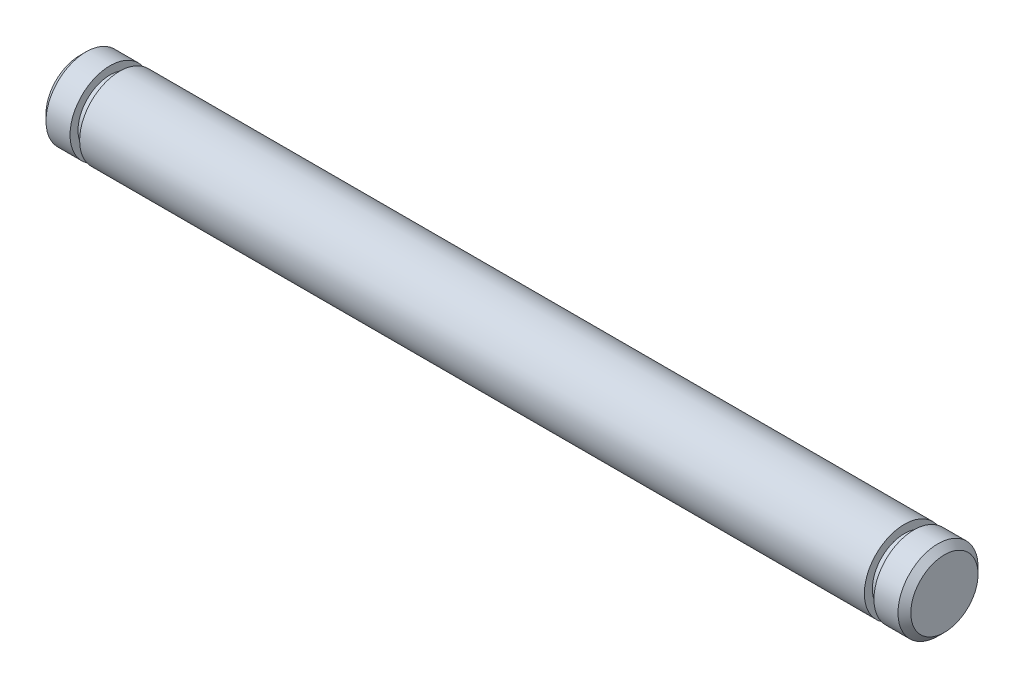
SolidWorks part; units mm, degrees
ref_plane "Front Plane" through (0, 0, 0) normal (0, 0, 1) x (1, 0, 0)
ref_plane "Top Plane" through (0, 0, 0) normal (0, 1, 0) x (1, 0, 0)
ref_plane "Right Plane" through (0, 0, 0) normal (1, 0, 0) x (0, 0, -1)
ref_axis "Axis_X" through (-4.6, 0, 0) along (1, 0, 0)
ref_axis "Axis_Y" through (0, 2.75, 0) along (0, -1, 0)
ref_axis "Axis_Z" through (0, 0, -2.75) along (0, 0, 1)
sketch "Sketch1" plane through (0, 0, 0) normal (0, 0, 1) x (1, 0, 0)
  line L0 (0.6, 2.5) -> (49.6, 2.5)
  line L1 (-1.9, 0) -> (52.1, 0) construction
  line L2 (-1.9, 0) -> (-1.9, 2.1)
  line L3 (-1.5, 2.5) -> (0, 2.5)
  line L4 (52.1, 0) -> (52.1, 2.1)
  line L5 (50.2, 2.5) -> (51.7, 2.5)
  line L6 (0, 2.5) -> (0, 2)
  line L7 (0, 2) -> (0.6, 2)
  line L8 (0.6, 2.5) -> (0.6, 2)
  line L9 (-1.9, 2.1) -> (-1.5, 2.5)
  line L10 (49.6, 2.5) -> (49.6, 2)
  line L11 (49.6, 2) -> (50.2, 2)
  line L12 (50.2, 2.5) -> (50.2, 2)
  line L13 (51.7, 2.5) -> (52.1, 2.1)
  line L14 (-1.9, 0) -> (52.1, 0)
  point P1 (52.1, 2.5)
  point P2 (-1.9, 2.5)
  dimension "MSM_3" = 54
  dimension "FIX_37" = 5
  dimension "FIX_31" = 2.5
  dimension "FIX_32" = 0.6
  dimension "FIX_38" = 4
  dimension "FIX_33" = 0.4
  dimension "FIX_34" = 0.4
  dimension "FIX_35" = 0.4
  dimension "FIX_36" = 0.4
revolve "Revolve1" add sketch "Sketch1" angle 360 about axis through (-4.6, 0, 0) along (1, 0, 0)
equation "\"Factor\"= 1.082532"
